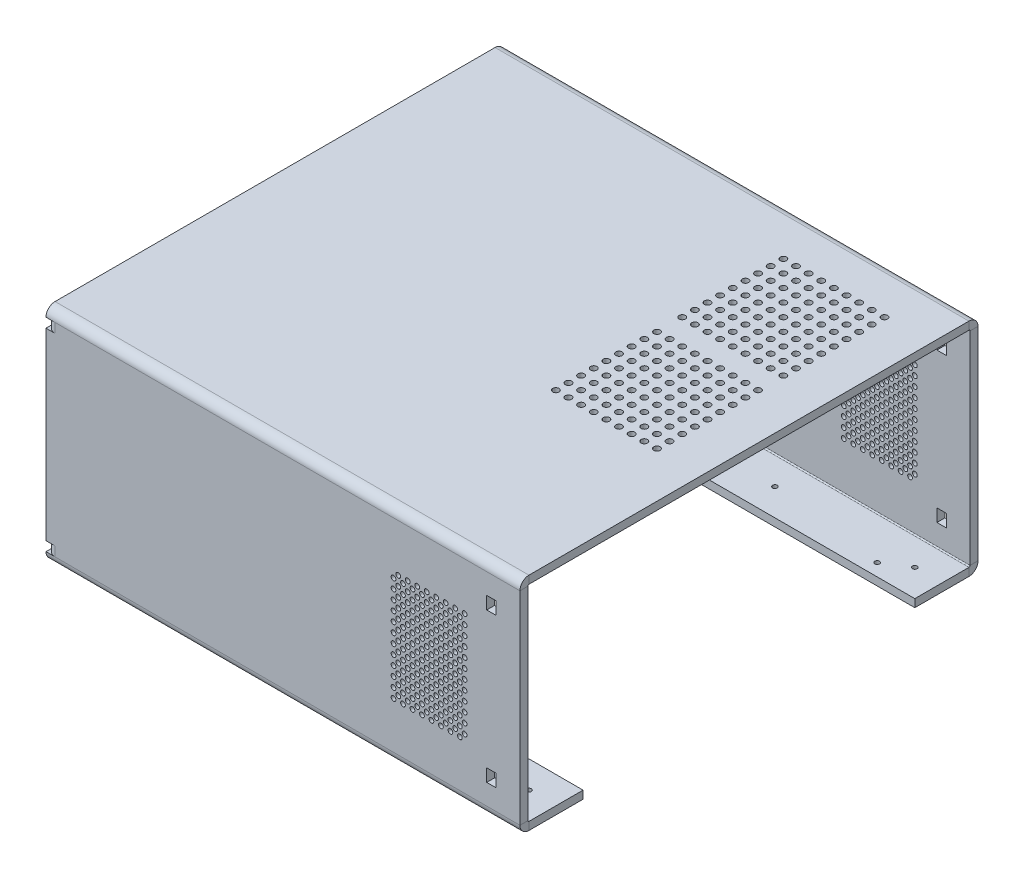
SolidWorks part; units mm, degrees
note: The reader was unsure of these and kept them because the rebuilt part matched: flange length of "Sides", "Bottom surfaces", "Edge-Flange4", "Edge-Flange5", "Edge-Flange6", "Edge-Flange7".
ref_plane "Front Plane" through (0, 0, 0) normal (0, 0, 1) x (1, 0, 0)
ref_plane "Top Plane" through (0, 0, 0) normal (0, 1, 0) x (1, 0, 0)
ref_plane "Right Plane" through (0, 0, 0) normal (1, 0, 0) x (0, 0, -1)
sketch "Sketch1" plane through (0, 0, 0) normal (0, 1, 0) x (1, 0, 0)
  line L1 (0, 0) -> (300, 0)
  line L2 (0, 0) -> (0, -280)
  line L3 (0, -280) -> (300, -280)
  line L4 (300, 0) -> (300, -280)
  dimension "D1" = 300
  dimension "D2" = 280
base flange "Top Surface" sketch "Sketch1" thickness 5 reverse thickness direction no parameters "D1"=0.7366
edge flange "Sides" sketch "Sketch10" flange profiles "Sketch10", "Sketch11" flange angle 90 flange length 140 flange position material outside bend radius 0.7366 thickness 5 relief rectangular parameters "D6"=10, "D8"=1
sketch "Sketch10" plane through (0, -5, 280) normal (0, 0, 1) x (-1, 0, 0)
  line L0 (0, 0) -> (-300, 0) construction
  line L1 (0, 0) -> (-300, 0)
  line L2 (-300, 0) -> (-300, 135)
  line L3 (-300, 135) -> (0, 135)
  line L4 (0, 135) -> (0, 0)
  dimension "D1" = 135
sketch "Sketch11" plane through (0, -5, 0) normal (0, 0, -1) x (1, 0, 0)
  line L0 (300, 0) -> (0, 0) construction
  line L1 (300, 0) -> (0, 0)
  line L2 (0, 0) -> (0, 135)
  line L3 (0, 135) -> (300, 135)
  line L4 (300, 135) -> (300, 0)
  line L7 (300, 135) -> (0, 135) construction
bend "EdgeBend1" bend radius 0.7366 bend angle 90 parameters "D5"=1
bend "EdgeBend2" bend radius 0.7366 bend angle 90 parameters "D5"=2
edge flange "Bottom surfaces" sketch "Sketch16" flange profiles "Sketch16", "Sketch17" flange angle 90 flange length 40 bend radius 0.7366 thickness 5 relief rectangular parameters "D6"=10, "D8"=1
sketch "Sketch16" plane through (0, -140, 280) normal (0, -1, 0) x (-1, 0, 0)
  line L2 (-300, 0) -> (-300, 35)
  line L3 (-300, 35) -> (0, 35)
  line L4 (0, 35) -> (0, 0)
  line L7 (0, 0) -> (-300, 0) construction
  line L8 (0, 0) -> (-300, 0)
sketch "Sketch17" plane through (0, -140, 0) normal (0, -1, 0) x (1, 0, 0)
  line L0 (300, 0) -> (0, 0) construction
  line L1 (300, 0) -> (0, 0)
  line L2 (0, 0) -> (0, 35)
  line L3 (0, 35) -> (300, 35)
  line L4 (300, 35) -> (300, 0)
bend "EdgeBend3" bend radius 0.7366 bend angle 90 parameters "D5"=3
bend "EdgeBend4" bend radius 0.7366 bend angle 90 parameters "D5"=4
sketch "Sketch27" plane through (0, -135, 0) normal (0, 1, 0) x (1, 0, 0)
  line L0 (17.1317, -17.8683) -> (17.1317, -262.1317) construction
  line L1 (17.1317, -262.1317) -> (105.7106, -262.1317) construction
  line L2 (105.7106, -262.1317) -> (194.2894, -262.1317) construction
  line L3 (194.2894, -262.1317) -> (282.8683, -262.1317) construction
  line L4 (282.8683, -262.1317) -> (282.8683, -17.8683) construction
  line L5 (282.8683, -17.8683) -> (194.2894, -17.8683) construction
  line L6 (194.2894, -17.8683) -> (105.7106, -17.8683) construction
  line L7 (105.7106, -17.8683) -> (105.7106, -262.1317) construction
  line L8 (17.1317, -17.8683) -> (105.7106, -17.8683) construction
  line L9 (194.2894, -17.8683) -> (194.2894, -262.1317) construction
  line L10 (17.1317, -17.8683) -> (0, -17.8683) construction
  line L11 (0, -35) -> (0, -0.7366) construction
  line L12 (282.8683, -17.8683) -> (300, -17.8683) construction
  line L13 (300, -0.7366) -> (300, -35) construction
  line L14 (17.1317, -17.8683) -> (17.1317, 5) construction
  line L15 (300, 5) -> (0, 5) construction
  line L16 (17.1317, -262.1317) -> (17.1317, -285) construction
  line L17 (0, -285) -> (300, -285) construction
  line L18 (17.1317, -262.1317) -> (0, -245) construction
  line L19 (17.1317, -262.1317) -> (0, -279.2634) construction
  line L20 (17.1317, -262.1317) -> (0, -262.1317) construction
  line L21 (0, -279.2634) -> (0, -245) construction
  line L22 (105.7106, -262.1317) -> (105.7106, -279.2634) construction
  line L23 (300, -279.2634) -> (0, -279.2634) construction
  circle A0 centre (17.1317, -17.8683) radius 1.5
  circle A1 centre (105.7106, -17.8683) radius 1.5
  circle A2 centre (194.2894, -17.8683) radius 1.5
  circle A3 centre (282.8683, -17.8683) radius 1.5
  circle A4 centre (17.1317, -262.1317) radius 1.5
  circle A5 centre (105.7106, -262.1317) radius 1.5
  circle A6 centre (194.2894, -262.1317) radius 1.5
  circle A7 centre (282.8683, -262.1317) radius 1.5
  dimension "D1" = 3
extrude "Screw Holes Bottom" cut sketch "Sketch27" against normal up to surface (5 mm away) normal cut yes up to face at (150, -140, 262.1317)
edge flange "Edge-Flange4" sketch "Sketch30" flange angle 90 flange length 11 flange position material inside bend radius 0.7366 thickness 5 relief none parameters "D6"=10
sketch "Sketch30" plane through (0, 0, 280) normal (-1, 0, 0) x (0, 1, 0)
  line L0 (-5.7366, 0) -> (-134.2634, 0) construction
  line L1 (-5.7366, 0) -> (-11.7366, 0)
  line L2 (-11.7366, 0) -> (-11.7366, 6)
  line L3 (-11.7366, 6) -> (-5.7366, 6)
  line L4 (-5.7366, 6) -> (-5.7366, 0)
  dimension "D1" = 6
  dimension "D2" = 6
bend "EdgeBend6" bend radius 0.7366 bend angle 90 parameters "D5"=5
edge flange "Edge-Flange5" sketch "Sketch33" flange angle 90 flange length 11 bend radius 0.7366 thickness 5 parameters "D6"=10
sketch "Sketch33" plane through (0, 0, 280) normal (-1, 0, 0) x (0, 1, 0)
  line L2 (-134.2634, 0) -> (-134.2634, 6)
  line L3 (-134.2634, 6) -> (-128.2634, 6)
  line L4 (-128.2634, 6) -> (-128.2634, 0)
  line L7 (-11.7366, 0) -> (-134.2634, 0) construction
  line L8 (-128.2634, 0) -> (-134.2634, 0)
  dimension "D1" = 6
  dimension "D2" = 6
bend "EdgeBend7" bend radius 0.7366 bend angle 90 parameters "D5"=6
edge flange "Edge-Flange6" sketch "Sketch36" flange angle 90 flange length 11 bend radius 0.7366 thickness 5 relief none parameters "D6"=10
sketch "Sketch36" plane through (0, 0, 0) normal (-1, 0, 0) x (0, -1, 0)
  line L0 (134.2634, 0) -> (5.7366, 0) construction
  line L1 (134.2634, 0) -> (128.2634, 0)
  line L2 (128.2634, 0) -> (128.2634, 6)
  line L3 (128.2634, 6) -> (134.2634, 6)
  line L4 (134.2634, 6) -> (134.2634, 0)
  dimension "D1" = 6
  dimension "D2" = 6
bend "EdgeBend8" bend radius 0.7366 bend angle 90 parameters "D5"=7
edge flange "Edge-Flange7" sketch "Sketch39" flange angle 90 flange length 11 bend radius 0.7366 thickness 5 relief none parameters "D6"=10
sketch "Sketch39" plane through (0, 0, 0) normal (-1, 0, 0) x (0, -1, 0)
  line L2 (5.7366, 0) -> (5.7366, 6)
  line L3 (5.7366, 6) -> (11.7366, 6)
  line L4 (11.7366, 6) -> (11.7366, 0)
  line L7 (128.2634, 0) -> (5.7366, 0) construction
  line L8 (11.7366, 0) -> (5.7366, 0)
  dimension "D1" = 6
  dimension "D2" = 6
bend "EdgeBend9" bend radius 0.7366 bend angle 90 parameters "D5"=8
sketch "Sketch40" plane through (0, 0, 0) normal (-1, 0, 0) x (0, 0, 1)
  line L0 (0.7366, -5.7366) -> (6, -11.7366) construction
  line L1 (6, -5.7366) -> (0.7366, -11.7366) construction
  line L4 (0.7366, -134.2634) -> (6, -128.2634) construction
  line L5 (0.7366, -128.2634) -> (6, -134.2634) construction
  line L6 (274, -128.2634) -> (279.2634, -134.2634) construction
  line L7 (279.2634, -128.2634) -> (274, -134.2634) construction
  line L8 (274, -134.2634) -> (279.2634, -134.2634) construction
  line L9 (274, -5.7366) -> (279.2634, -11.7366) construction
  line L10 (279.2634, -5.7366) -> (274, -11.7366) construction
  circle A0 centre (3.3683, -8.7366) radius 1.5
  circle A1 centre (3.3683, -131.2634) radius 1.5
  circle A2 centre (276.6317, -8.7366) radius 1.5
  circle A3 centre (276.6317, -131.2634) radius 1.5
  dimension "D1" = 3
extrude "Cut-Extrude3" cut sketch "Sketch40" against normal up to surface (5 mm away) normal cut yes up to face at (5, -8.7366, 3.3683)
sketch "Sketch42" plane through (0, 0, -5) normal (0, 0, -1) x (-1, 0, 0)
  line L0 (-265, -35.7366) -> (-265, -5.7366) construction
  line L1 (-300, -5.7366) -> (-5.7366, -5.7366) construction
  line L2 (-265, -35.7366) -> (-300, -35.7366) construction
  line L3 (-300, -5.7366) -> (-300, -134.2634) construction
  line L4 (-265, -35.7366) -> (-259, -35.7366) construction
  line L5 (-262, -38.7366) -> (-262, -35.7366) construction
  line L6 (-262, -38.7366) -> (-265, -35.7366) construction
  line L7 (-259, -35.7366) -> (-262, -38.7366) construction
  line L8 (-265, -41.7366) -> (-265, -11.7366) construction
  line L9 (-265, -53.7366) -> (-265, -23.7366) construction
  line L10 (-265, -53.7366) -> (-300, -53.7366) construction
  line L11 (-265, -53.7366) -> (-259, -53.7366) construction
  line L12 (-262, -56.7366) -> (-262, -53.7366) construction
  line L14 (-262, -56.7366) -> (-265, -53.7366) construction
  line L20 (-265, -47.7366) -> (-300, -47.7366) construction
  line L21 (-265, -41.7366) -> (-300, -41.7366) construction
  line L22 (-265, -47.7366) -> (-265, -17.7366) construction
  line L23 (-265, -41.7366) -> (-259, -41.7366) construction
  line L24 (-262, -44.7366) -> (-262, -41.7366) construction
  line L25 (-262, -44.7366) -> (-265, -41.7366) construction
  line L26 (-259, -41.7366) -> (-262, -44.7366) construction
  line L27 (-265, -47.7366) -> (-259, -47.7366) construction
  line L28 (-262, -50.7366) -> (-262, -47.7366) construction
  line L29 (-259, -47.7366) -> (-262, -50.7366) construction
  line L30 (-262, -50.7366) -> (-265, -47.7366) construction
  line L31 (-259, -53.7366) -> (-262, -56.7366) construction
  line L32 (-265, -59.7366) -> (-265, -29.7366) construction
  line L33 (-265, -59.7366) -> (-300, -59.7366) construction
  line L34 (-265, -59.7366) -> (-259, -59.7366) construction
  line L35 (-262, -62.7366) -> (-262, -59.7366) construction
  line L36 (-262, -62.7366) -> (-265, -59.7366) construction
  line L37 (-259, -59.7366) -> (-262, -62.7366) construction
  line L38 (-265, -65.7366) -> (-265, -35.7366) construction
  line L39 (-265, -65.7366) -> (-300, -65.7366) construction
  line L40 (-265, -65.7366) -> (-259, -65.7366) construction
  line L41 (-262, -68.7366) -> (-262, -65.7366) construction
  line L42 (-262, -68.7366) -> (-265, -65.7366) construction
  line L43 (-259, -65.7366) -> (-262, -68.7366) construction
  line L44 (-265, -71.7366) -> (-265, -41.7366) construction
  line L45 (-265, -71.7366) -> (-300, -71.7366) construction
  line L46 (-265, -71.7366) -> (-259, -71.7366) construction
  line L47 (-262, -74.7366) -> (-262, -71.7366) construction
  line L48 (-262, -74.7366) -> (-265, -71.7366) construction
  line L49 (-259, -71.7366) -> (-262, -74.7366) construction
  line L50 (-265, -77.7366) -> (-265, -47.7366) construction
  line L51 (-265, -77.7366) -> (-300, -77.7366) construction
  line L52 (-265, -77.7366) -> (-259, -77.7366) construction
  line L53 (-262, -80.7366) -> (-262, -77.7366) construction
  line L54 (-262, -80.7366) -> (-265, -77.7366) construction
  line L55 (-259, -77.7366) -> (-262, -80.7366) construction
  line L56 (-265, -83.7366) -> (-265, -53.7366) construction
  line L57 (-265, -83.7366) -> (-300, -83.7366) construction
  line L58 (-265, -83.7366) -> (-259, -83.7366) construction
  line L59 (-262, -86.7366) -> (-262, -83.7366) construction
  line L60 (-262, -86.7366) -> (-265, -83.7366) construction
  line L61 (-259, -83.7366) -> (-262, -86.7366) construction
  line L62 (-265, -89.7366) -> (-265, -59.7366) construction
  line L63 (-265, -89.7366) -> (-300, -89.7366) construction
  line L64 (-265, -89.7366) -> (-259, -89.7366) construction
  line L65 (-262, -92.7366) -> (-262, -89.7366) construction
  line L66 (-262, -92.7366) -> (-265, -89.7366) construction
  line L67 (-259, -89.7366) -> (-262, -92.7366) construction
  line L68 (-265, -95.7366) -> (-265, -65.7366) construction
  line L69 (-265, -95.7366) -> (-300, -95.7366) construction
  line L70 (-265, -95.7366) -> (-259, -95.7366) construction
  line L71 (-262, -98.7366) -> (-262, -95.7366) construction
  line L72 (-262, -98.7366) -> (-265, -95.7366) construction
  line L73 (-259, -95.7366) -> (-262, -98.7366) construction
  line L74 (-265, -101.7366) -> (-265, -71.7366) construction
  line L75 (-265, -101.7366) -> (-300, -101.7366) construction
  line L76 (-265, -101.7366) -> (-259, -101.7366) construction
  line L77 (-262, -104.7366) -> (-262, -101.7366) construction
  line L78 (-262, -104.7366) -> (-265, -101.7366) construction
  line L79 (-259, -101.7366) -> (-262, -104.7366) construction
  circle A0 centre (-265, -35.7366) radius 1.5
  circle A1 centre (-259, -35.7366) radius 1.5
  circle A2 centre (-253, -35.7366) radius 1.5
  circle A3 centre (-247, -35.7366) radius 1.5
  circle A4 centre (-241, -35.7366) radius 1.5
  circle A5 centre (-235, -35.7366) radius 1.5
  circle A6 centre (-229, -35.7366) radius 1.5
  circle A7 centre (-223, -35.7366) radius 1.5
  circle A16 centre (-262, -38.7366) radius 1.5
  circle A17 centre (-256, -38.7366) radius 1.5
  circle A18 centre (-250, -38.7366) radius 1.5
  circle A19 centre (-244, -38.7366) radius 1.5
  circle A20 centre (-238, -38.7366) radius 1.5
  circle A21 centre (-232, -38.7366) radius 1.5
  circle A22 centre (-226, -38.7366) radius 1.5
  circle A23 centre (-220, -38.7366) radius 1.5
  circle A24 centre (-265, -41.7366) radius 1.5
  circle A25 centre (-259, -41.7366) radius 1.5
  circle A26 centre (-253, -41.7366) radius 1.5
  circle A27 centre (-247, -41.7366) radius 1.5
  circle A28 centre (-241, -41.7366) radius 1.5
  circle A29 centre (-235, -41.7366) radius 1.5
  circle A30 centre (-229, -41.7366) radius 1.5
  circle A31 centre (-223, -41.7366) radius 1.5
  circle A32 centre (-262, -44.7366) radius 1.5
  circle A33 centre (-256, -44.7366) radius 1.5
  circle A34 centre (-250, -44.7366) radius 1.5
  circle A35 centre (-244, -44.7366) radius 1.5
  circle A36 centre (-238, -44.7366) radius 1.5
  circle A37 centre (-232, -44.7366) radius 1.5
  circle A38 centre (-226, -44.7366) radius 1.5
  circle A39 centre (-220, -44.7366) radius 1.5
  circle A40 centre (-265, -47.7366) radius 1.5
  circle A41 centre (-259, -47.7366) radius 1.5
  circle A42 centre (-253, -47.7366) radius 1.5
  circle A43 centre (-247, -47.7366) radius 1.5
  circle A44 centre (-241, -47.7366) radius 1.5
  circle A45 centre (-235, -47.7366) radius 1.5
  circle A46 centre (-229, -47.7366) radius 1.5
  circle A47 centre (-223, -47.7366) radius 1.5
  circle A48 centre (-262, -50.7366) radius 1.5
  circle A49 centre (-256, -50.7366) radius 1.5
  circle A50 centre (-250, -50.7366) radius 1.5
  circle A51 centre (-244, -50.7366) radius 1.5
  circle A52 centre (-238, -50.7366) radius 1.5
  circle A53 centre (-232, -50.7366) radius 1.5
  circle A54 centre (-226, -50.7366) radius 1.5
  circle A55 centre (-220, -50.7366) radius 1.5
  circle A56 centre (-265, -53.7366) radius 1.5
  circle A57 centre (-259, -53.7366) radius 1.5
  circle A58 centre (-253, -53.7366) radius 1.5
  circle A59 centre (-247, -53.7366) radius 1.5
  circle A60 centre (-241, -53.7366) radius 1.5
  circle A61 centre (-235, -53.7366) radius 1.5
  circle A62 centre (-229, -53.7366) radius 1.5
  circle A63 centre (-223, -53.7366) radius 1.5
  circle A64 centre (-262, -56.7366) radius 1.5
  circle A65 centre (-256, -56.7366) radius 1.5
  circle A66 centre (-250, -56.7366) radius 1.5
  circle A67 centre (-244, -56.7366) radius 1.5
  circle A68 centre (-238, -56.7366) radius 1.5
  circle A69 centre (-232, -56.7366) radius 1.5
  circle A70 centre (-226, -56.7366) radius 1.5
  circle A71 centre (-220, -56.7366) radius 1.5
  circle A72 centre (-265, -59.7366) radius 1.5
  circle A73 centre (-259, -59.7366) radius 1.5
  circle A74 centre (-253, -59.7366) radius 1.5
  circle A75 centre (-247, -59.7366) radius 1.5
  circle A76 centre (-241, -59.7366) radius 1.5
  circle A77 centre (-235, -59.7366) radius 1.5
  circle A78 centre (-229, -59.7366) radius 1.5
  circle A79 centre (-223, -59.7366) radius 1.5
  circle A80 centre (-262, -62.7366) radius 1.5
  circle A81 centre (-256, -62.7366) radius 1.5
  circle A82 centre (-250, -62.7366) radius 1.5
  circle A83 centre (-244, -62.7366) radius 1.5
  circle A84 centre (-238, -62.7366) radius 1.5
  circle A85 centre (-232, -62.7366) radius 1.5
  circle A86 centre (-226, -62.7366) radius 1.5
  circle A87 centre (-220, -62.7366) radius 1.5
  circle A88 centre (-265, -65.7366) radius 1.5
  circle A89 centre (-259, -65.7366) radius 1.5
  circle A90 centre (-253, -65.7366) radius 1.5
  circle A91 centre (-247, -65.7366) radius 1.5
  circle A92 centre (-241, -65.7366) radius 1.5
  circle A93 centre (-235, -65.7366) radius 1.5
  circle A94 centre (-229, -65.7366) radius 1.5
  circle A95 centre (-223, -65.7366) radius 1.5
  circle A96 centre (-262, -68.7366) radius 1.5
  circle A97 centre (-256, -68.7366) radius 1.5
  circle A98 centre (-250, -68.7366) radius 1.5
  circle A99 centre (-244, -68.7366) radius 1.5
  circle A100 centre (-238, -68.7366) radius 1.5
  circle A101 centre (-232, -68.7366) radius 1.5
  circle A102 centre (-226, -68.7366) radius 1.5
  circle A103 centre (-220, -68.7366) radius 1.5
  circle A104 centre (-265, -71.7366) radius 1.5
  circle A105 centre (-259, -71.7366) radius 1.5
  circle A106 centre (-253, -71.7366) radius 1.5
  circle A107 centre (-247, -71.7366) radius 1.5
  circle A108 centre (-241, -71.7366) radius 1.5
  circle A109 centre (-235, -71.7366) radius 1.5
  circle A110 centre (-229, -71.7366) radius 1.5
  circle A111 centre (-223, -71.7366) radius 1.5
  circle A112 centre (-262, -74.7366) radius 1.5
  circle A113 centre (-256, -74.7366) radius 1.5
  circle A114 centre (-250, -74.7366) radius 1.5
  circle A115 centre (-244, -74.7366) radius 1.5
  circle A116 centre (-238, -74.7366) radius 1.5
  circle A117 centre (-232, -74.7366) radius 1.5
  circle A118 centre (-226, -74.7366) radius 1.5
  circle A119 centre (-220, -74.7366) radius 1.5
  circle A120 centre (-265, -77.7366) radius 1.5
  circle A121 centre (-259, -77.7366) radius 1.5
  circle A122 centre (-253, -77.7366) radius 1.5
  circle A123 centre (-247, -77.7366) radius 1.5
  circle A124 centre (-241, -77.7366) radius 1.5
  circle A125 centre (-235, -77.7366) radius 1.5
  circle A126 centre (-229, -77.7366) radius 1.5
  circle A127 centre (-223, -77.7366) radius 1.5
  circle A128 centre (-262, -80.7366) radius 1.5
  circle A129 centre (-256, -80.7366) radius 1.5
  circle A130 centre (-250, -80.7366) radius 1.5
  circle A131 centre (-244, -80.7366) radius 1.5
  circle A132 centre (-238, -80.7366) radius 1.5
  circle A133 centre (-232, -80.7366) radius 1.5
  circle A134 centre (-226, -80.7366) radius 1.5
  circle A135 centre (-220, -80.7366) radius 1.5
  circle A136 centre (-265, -83.7366) radius 1.5
  circle A137 centre (-259, -83.7366) radius 1.5
  circle A138 centre (-253, -83.7366) radius 1.5
  circle A139 centre (-247, -83.7366) radius 1.5
  circle A140 centre (-241, -83.7366) radius 1.5
  circle A141 centre (-235, -83.7366) radius 1.5
  circle A142 centre (-229, -83.7366) radius 1.5
  circle A143 centre (-223, -83.7366) radius 1.5
  circle A144 centre (-262, -86.7366) radius 1.5
  circle A145 centre (-256, -86.7366) radius 1.5
  circle A146 centre (-250, -86.7366) radius 1.5
  circle A147 centre (-244, -86.7366) radius 1.5
  circle A148 centre (-238, -86.7366) radius 1.5
  circle A149 centre (-232, -86.7366) radius 1.5
  circle A150 centre (-226, -86.7366) radius 1.5
  circle A151 centre (-220, -86.7366) radius 1.5
  circle A152 centre (-265, -89.7366) radius 1.5
  circle A153 centre (-259, -89.7366) radius 1.5
  circle A154 centre (-253, -89.7366) radius 1.5
  circle A155 centre (-247, -89.7366) radius 1.5
  circle A156 centre (-241, -89.7366) radius 1.5
  circle A157 centre (-235, -89.7366) radius 1.5
  circle A158 centre (-229, -89.7366) radius 1.5
  circle A159 centre (-223, -89.7366) radius 1.5
  circle A160 centre (-262, -92.7366) radius 1.5
  circle A161 centre (-256, -92.7366) radius 1.5
  circle A162 centre (-250, -92.7366) radius 1.5
  circle A163 centre (-244, -92.7366) radius 1.5
  circle A164 centre (-238, -92.7366) radius 1.5
  circle A165 centre (-232, -92.7366) radius 1.5
  circle A166 centre (-226, -92.7366) radius 1.5
  circle A167 centre (-220, -92.7366) radius 1.5
  circle A168 centre (-265, -95.7366) radius 1.5
  circle A169 centre (-259, -95.7366) radius 1.5
  circle A170 centre (-253, -95.7366) radius 1.5
  circle A171 centre (-247, -95.7366) radius 1.5
  circle A172 centre (-241, -95.7366) radius 1.5
  circle A173 centre (-235, -95.7366) radius 1.5
  circle A174 centre (-229, -95.7366) radius 1.5
  circle A175 centre (-223, -95.7366) radius 1.5
  circle A176 centre (-262, -98.7366) radius 1.5
  circle A177 centre (-256, -98.7366) radius 1.5
  circle A178 centre (-250, -98.7366) radius 1.5
  circle A179 centre (-244, -98.7366) radius 1.5
  circle A180 centre (-238, -98.7366) radius 1.5
  circle A181 centre (-232, -98.7366) radius 1.5
  circle A182 centre (-226, -98.7366) radius 1.5
  circle A183 centre (-220, -98.7366) radius 1.5
  circle A184 centre (-265, -101.7366) radius 1.5
  circle A185 centre (-259, -101.7366) radius 1.5
  circle A186 centre (-253, -101.7366) radius 1.5
  circle A187 centre (-247, -101.7366) radius 1.5
  circle A188 centre (-241, -101.7366) radius 1.5
  circle A189 centre (-235, -101.7366) radius 1.5
  circle A190 centre (-229, -101.7366) radius 1.5
  circle A191 centre (-223, -101.7366) radius 1.5
  circle A192 centre (-262, -104.7366) radius 1.5
  circle A193 centre (-256, -104.7366) radius 1.5
  circle A194 centre (-250, -104.7366) radius 1.5
  circle A195 centre (-244, -104.7366) radius 1.5
  circle A196 centre (-238, -104.7366) radius 1.5
  circle A197 centre (-232, -104.7366) radius 1.5
  circle A198 centre (-226, -104.7366) radius 1.5
  circle A199 centre (-220, -104.7366) radius 1.5
  dimension "D1" = 3
  dimension "D5" = 3
  dimension "D6" = 3
  dimension "D2" = 35
  dimension "D3" = 30
  dimension "D7" = 8
  dimension "D4" = 8
  dimension "D8" = 12
extrude "Side Air Vents" cut sketch "Sketch42" against normal through all normal cut yes
sketch "Sketch46" plane through (0, 0, 0) normal (0, 1, 0) x (1, 0, 0)
  line L0 (200.7643, -140) -> (200.7643, -0.7366) construction
  line L1 (300, -0.7366) -> (0, -0.7366) construction
  line L2 (200.7643, -140) -> (200.7643, -279.2634) construction
  line L3 (0, -279.2634) -> (300, -279.2634) construction
  circle A4 centre (207.1214, -25.3668) radius 2
  circle A8 centre (207.1214, -33.3668) radius 2
  circle A12 centre (207.1214, -41.3668) radius 2
  circle A16 centre (207.1214, -49.3668) radius 2
  circle A20 centre (207.1214, -57.3668) radius 2
  circle A21 centre (207.1214, -65.3668) radius 2
  circle A22 centre (207.1214, -73.3668) radius 2
  circle A23 centre (207.1214, -81.3668) radius 2
  circle A24 centre (207.1214, -89.3668) radius 2
  circle A25 centre (215.1214, -25.3668) radius 2
  circle A26 centre (215.1214, -33.3668) radius 2
  circle A27 centre (215.1214, -41.3668) radius 2
  circle A28 centre (215.1214, -49.3668) radius 2
  circle A29 centre (215.1214, -57.3668) radius 2
  circle A30 centre (215.1214, -65.3668) radius 2
  circle A31 centre (215.1214, -73.3668) radius 2
  circle A32 centre (215.1214, -81.3668) radius 2
  circle A33 centre (215.1214, -89.3668) radius 2
  circle A34 centre (223.1214, -25.3668) radius 2
  circle A35 centre (223.1214, -33.3668) radius 2
  circle A36 centre (223.1214, -41.3668) radius 2
  circle A37 centre (223.1214, -49.3668) radius 2
  circle A38 centre (223.1214, -57.3668) radius 2
  circle A39 centre (223.1214, -65.3668) radius 2
  circle A40 centre (223.1214, -73.3668) radius 2
  circle A41 centre (223.1214, -81.3668) radius 2
  circle A42 centre (223.1214, -89.3668) radius 2
  circle A43 centre (231.1214, -25.3668) radius 2
  circle A44 centre (231.1214, -33.3668) radius 2
  circle A45 centre (231.1214, -41.3668) radius 2
  circle A46 centre (231.1214, -49.3668) radius 2
  circle A47 centre (231.1214, -57.3668) radius 2
  circle A48 centre (231.1214, -65.3668) radius 2
  circle A49 centre (231.1214, -73.3668) radius 2
  circle A50 centre (231.1214, -81.3668) radius 2
  circle A51 centre (231.1214, -89.3668) radius 2
  circle A52 centre (239.1214, -25.3668) radius 2
  circle A53 centre (239.1214, -33.3668) radius 2
  circle A54 centre (239.1214, -41.3668) radius 2
  circle A55 centre (239.1214, -49.3668) radius 2
  circle A56 centre (239.1214, -57.3668) radius 2
  circle A57 centre (239.1214, -65.3668) radius 2
  circle A58 centre (239.1214, -73.3668) radius 2
  circle A59 centre (239.1214, -81.3668) radius 2
  circle A60 centre (239.1214, -89.3668) radius 2
  circle A61 centre (247.1214, -25.3668) radius 2
  circle A62 centre (247.1214, -33.3668) radius 2
  circle A63 centre (247.1214, -41.3668) radius 2
  circle A64 centre (247.1214, -49.3668) radius 2
  circle A65 centre (247.1214, -57.3668) radius 2
  circle A66 centre (247.1214, -65.3668) radius 2
  circle A67 centre (247.1214, -73.3668) radius 2
  circle A68 centre (247.1214, -81.3668) radius 2
  circle A69 centre (247.1214, -89.3668) radius 2
  circle A70 centre (255.1214, -25.3668) radius 2
  circle A71 centre (255.1214, -33.3668) radius 2
  circle A72 centre (255.1214, -41.3668) radius 2
  circle A73 centre (255.1214, -49.3668) radius 2
  circle A74 centre (255.1214, -57.3668) radius 2
  circle A75 centre (255.1214, -65.3668) radius 2
  circle A76 centre (255.1214, -73.3668) radius 2
  circle A77 centre (255.1214, -81.3668) radius 2
  circle A78 centre (255.1214, -89.3668) radius 2
  circle A79 centre (263.1214, -25.3668) radius 2
  circle A80 centre (263.1214, -33.3668) radius 2
  circle A81 centre (263.1214, -41.3668) radius 2
  circle A82 centre (263.1214, -49.3668) radius 2
  circle A83 centre (263.1214, -57.3668) radius 2
  circle A84 centre (263.1214, -65.3668) radius 2
  circle A85 centre (263.1214, -73.3668) radius 2
  circle A86 centre (263.1214, -81.3668) radius 2
  circle A87 centre (263.1214, -89.3668) radius 2
  circle A88 centre (271.1214, -25.3668) radius 2
  circle A89 centre (271.1214, -33.3668) radius 2
  circle A90 centre (271.1214, -41.3668) radius 2
  circle A91 centre (271.1214, -49.3668) radius 2
  circle A92 centre (271.1214, -57.3668) radius 2
  circle A93 centre (271.1214, -65.3668) radius 2
  circle A94 centre (271.1214, -73.3668) radius 2
  circle A95 centre (271.1214, -81.3668) radius 2
  circle A96 centre (271.1214, -89.3668) radius 2
  circle A97 centre (207.1214, -105.3668) radius 2
  circle A98 centre (207.1214, -113.3668) radius 2
  circle A99 centre (207.1214, -121.3668) radius 2
  circle A100 centre (207.1214, -129.3668) radius 2
  circle A101 centre (207.1214, -137.3668) radius 2
  circle A102 centre (207.1214, -145.3668) radius 2
  circle A103 centre (207.1214, -153.3668) radius 2
  circle A104 centre (207.1214, -161.3668) radius 2
  circle A105 centre (207.1214, -169.3668) radius 2
  circle A106 centre (215.1214, -105.3668) radius 2
  circle A107 centre (215.1214, -113.3668) radius 2
  circle A108 centre (215.1214, -121.3668) radius 2
  circle A109 centre (215.1214, -129.3668) radius 2
  circle A110 centre (215.1214, -137.3668) radius 2
  circle A111 centre (215.1214, -145.3668) radius 2
  circle A112 centre (215.1214, -153.3668) radius 2
  circle A113 centre (215.1214, -161.3668) radius 2
  circle A114 centre (215.1214, -169.3668) radius 2
  circle A115 centre (223.1214, -105.3668) radius 2
  circle A116 centre (223.1214, -113.3668) radius 2
  circle A117 centre (223.1214, -121.3668) radius 2
  circle A118 centre (223.1214, -129.3668) radius 2
  circle A119 centre (223.1214, -137.3668) radius 2
  circle A120 centre (223.1214, -145.3668) radius 2
  circle A121 centre (223.1214, -153.3668) radius 2
  circle A122 centre (223.1214, -161.3668) radius 2
  circle A123 centre (223.1214, -169.3668) radius 2
  circle A124 centre (231.1214, -105.3668) radius 2
  circle A125 centre (231.1214, -113.3668) radius 2
  circle A126 centre (231.1214, -121.3668) radius 2
  circle A127 centre (231.1214, -129.3668) radius 2
  circle A128 centre (231.1214, -137.3668) radius 2
  circle A129 centre (231.1214, -145.3668) radius 2
  circle A130 centre (231.1214, -153.3668) radius 2
  circle A131 centre (231.1214, -161.3668) radius 2
  circle A132 centre (231.1214, -169.3668) radius 2
  circle A133 centre (239.1214, -105.3668) radius 2
  circle A134 centre (239.1214, -113.3668) radius 2
  circle A135 centre (239.1214, -121.3668) radius 2
  circle A136 centre (239.1214, -129.3668) radius 2
  circle A137 centre (239.1214, -137.3668) radius 2
  circle A138 centre (239.1214, -145.3668) radius 2
  circle A139 centre (239.1214, -153.3668) radius 2
  circle A140 centre (239.1214, -161.3668) radius 2
  circle A141 centre (239.1214, -169.3668) radius 2
  circle A142 centre (247.1214, -105.3668) radius 2
  circle A143 centre (247.1214, -113.3668) radius 2
  circle A144 centre (247.1214, -121.3668) radius 2
  circle A145 centre (247.1214, -129.3668) radius 2
  circle A146 centre (247.1214, -137.3668) radius 2
  circle A147 centre (247.1214, -145.3668) radius 2
  circle A148 centre (247.1214, -153.3668) radius 2
  circle A149 centre (247.1214, -161.3668) radius 2
  circle A150 centre (247.1214, -169.3668) radius 2
  circle A151 centre (255.1214, -105.3668) radius 2
  circle A152 centre (255.1214, -113.3668) radius 2
  circle A153 centre (255.1214, -121.3668) radius 2
  circle A154 centre (255.1214, -129.3668) radius 2
  circle A155 centre (255.1214, -137.3668) radius 2
  circle A156 centre (255.1214, -145.3668) radius 2
  circle A157 centre (255.1214, -153.3668) radius 2
  circle A158 centre (255.1214, -161.3668) radius 2
  circle A159 centre (255.1214, -169.3668) radius 2
  circle A160 centre (263.1214, -105.3668) radius 2
  circle A161 centre (263.1214, -113.3668) radius 2
  circle A162 centre (263.1214, -121.3668) radius 2
  circle A163 centre (263.1214, -129.3668) radius 2
  circle A164 centre (263.1214, -137.3668) radius 2
  circle A165 centre (263.1214, -145.3668) radius 2
  circle A166 centre (263.1214, -153.3668) radius 2
  circle A167 centre (263.1214, -161.3668) radius 2
  circle A168 centre (263.1214, -169.3668) radius 2
  circle A169 centre (271.1214, -105.3668) radius 2
  circle A170 centre (271.1214, -113.3668) radius 2
  circle A171 centre (271.1214, -121.3668) radius 2
  circle A172 centre (271.1214, -129.3668) radius 2
  circle A173 centre (271.1214, -137.3668) radius 2
  circle A174 centre (271.1214, -145.3668) radius 2
  circle A175 centre (271.1214, -153.3668) radius 2
  circle A176 centre (271.1214, -161.3668) radius 2
  circle A177 centre (271.1214, -169.3668) radius 2
  dimension "D1" = 9
  dimension "D2" = 2
extrude "Top Air Vents" cut sketch "Sketch46" against normal up to surface (5 mm away) normal cut yes up to face at (150, -5, 140)
sketch "Sketch43" plane through (0, 0, 285) normal (0, 0, 1) x (1, 0, 0)
  line L0 (279, -18.7366) -> (279, -5.7366) construction
  line L1 (279, -18.7366) -> (285, -18.7366)
  line L2 (279, -18.7366) -> (279, -26.7366)
  line L3 (279, -26.7366) -> (285, -26.7366)
  line L4 (285, -18.7366) -> (285, -26.7366)
  line L5 (279, -113.2634) -> (285, -113.2634)
  line L6 (279, -113.2634) -> (279, -121.2634)
  line L7 (279, -121.2634) -> (285, -121.2634)
  line L8 (285, -113.2634) -> (285, -121.2634)
  line L9 (5.7366, -5.7366) -> (300, -5.7366) construction
  line L10 (279, -121.2634) -> (279, -134.2634) construction
  line L11 (5.7366, -134.2634) -> (300, -134.2634) construction
  line L12 (300, -134.2634) -> (300, -5.7366) construction
  dimension "D1" = 6
  dimension "D2" = 8
  dimension "D3" = 13
  dimension "D4" = 15
extrude "Snap Hook Groves" cut sketch "Sketch43" against normal up to surface (290 mm away) up to face at (265, -82.2366, -5)
sketch "Sketch47" plane through (0, -135, 0) normal (0, 1, 0) x (1, 0, 0)
  circle A0 centre (268.313, -27.1322) radius 1.5
  circle A1 centre (31.763, -27.1322) radius 1.5
extrude "Cut-Extrude4" cut sketch "Sketch47" against normal blind 10
sketch "Bend-Lines1" [suppressed] plane through (0, 0, 0) normal (0, 1, 0) x (1, 0, 0)
sketch "Bounding-Box1" [suppressed] plane through (0, 0, 0) normal (0, 1, 0) x (1, 0, 0)
sheet metal parameters "Sheet-Metal1" thickness 5 parameters "D1"=0.7366
flat pattern "Flat-Pattern1" [suppressed]
sketch "Bend-Lines2" plane through (0, 0, 0) normal (0, 1, 0) x (1, 0, 0)
sketch3d "Bounding-Box2" [suppressed]
  line L0 (-300, -250, 0) -> (0, -250, 0) construction
  line L1 (-300, 0, 0) -> (0, 0, 0) construction
  line L2 (-300, -250, 0) -> (-300, 0, 0) construction
  line L3 (0, -250, 0) -> (0, 0, 0) construction
sheet metal parameters "Sheet-Metal2" thickness 5 parameters "D1"=0.7366
flat pattern "Flat-Pattern1" [suppressed]
sketch "Bend-Lines2" plane through (0, 0, 0) normal (0, 1, 0) x (1, 0, 0)
  line L0 (300, 1.8054) -> (0, 1.8054) construction
  line L1 (0, -251.8054) -> (300, -251.8054) construction
  line L2 (300, 1.8054) -> (0, 1.8054) construction
  line L3 (0, -251.8054) -> (300, -251.8054) construction
sketch3d "Bounding-Box2" [suppressed]
  line L0 (0, 98.6108, 0) -> (0, -348.6108, 0) construction
  line L1 (300, 98.6108, 0) -> (300, -348.6108, 0) construction
  line L2 (0, 98.6108, 0) -> (300, 98.6108, 0) construction
  line L3 (0, -348.6108, 0) -> (300, -348.6108, 0) construction
bend of the flat pattern "Flatten-<EdgeBend1>1"
bend of the flat pattern "Flatten-<EdgeBend2>1"
sheet metal parameters "Sheet-Metal3" thickness 5 parameters "D1"=0.7366
flat pattern "Flat-Pattern1" [suppressed]
sketch "Bend-Lines2" plane through (0, 0, 0) normal (0, 1, 0) x (1, 0, 0)
  line L0 (300, 1.8054) -> (0, 1.8054) construction
  line L1 (0, -251.8054) -> (300, -251.8054) construction
  line L2 (300, 1.8054) -> (0, 1.8054) construction
  line L3 (0, -251.8054) -> (300, -251.8054) construction
  line L4 (300, 100.4163) -> (0, 100.4163) construction
  line L5 (0, -350.4163) -> (300, -350.4163) construction
  line L6 (300, 100.4163) -> (0, 100.4163) construction
  line L7 (0, -350.4163) -> (300, -350.4163) construction
sketch3d "Bounding-Box2" [suppressed]
  line L0 (0, 137.2217, 0) -> (0, -387.2217, 0) construction
  line L1 (300, 137.2217, 0) -> (300, -387.2217, 0) construction
  line L2 (0, 137.2217, 0) -> (300, 137.2217, 0) construction
  line L3 (0, -387.2217, 0) -> (300, -387.2217, 0) construction
bend of the flat pattern "Flatten-<EdgeBend3>1"
bend of the flat pattern "Flatten-<EdgeBend4>1"
bend of the flat pattern "Flatten-<EdgeBend1>1"
bend of the flat pattern "Flatten-<EdgeBend2>1"
sheet metal parameters "Sheet-Metal7" thickness 5 parameters "D1"=0.7366
flat pattern "Flat-Pattern1" [suppressed]
sketch "Bend-Lines2" plane through (0, 0, 0) normal (0, 1, 0) x (1, 0, 0)
  line L0 (300, 1.8054) -> (0, 1.8054) construction
  line L1 (0, -251.8054) -> (300, -251.8054) construction
  line L2 (300, 1.8054) -> (0, 1.8054) construction
  line L3 (0, -251.8054) -> (300, -251.8054) construction
  line L4 (300, 100.4163) -> (0, 100.4163) construction
  line L5 (0, -350.4163) -> (300, -350.4163) construction
  line L6 (300, 100.4163) -> (0, 100.4163) construction
  line L7 (0, -350.4163) -> (300, -350.4163) construction
sketch3d "Bounding-Box2" [suppressed]
  line L0 (0, 137.2217, 0) -> (0, -387.2217, 0) construction
  line L1 (300, 137.2217, 0) -> (300, -387.2217, 0) construction
  line L2 (0, 137.2217, 0) -> (300, 137.2217, 0) construction
  line L3 (0, -387.2217, 0) -> (300, -387.2217, 0) construction
bend of the flat pattern "Flatten-<EdgeBend3>1"
bend of the flat pattern "Flatten-<EdgeBend4>1"
bend of the flat pattern "Flatten-<EdgeBend1>1"
bend of the flat pattern "Flatten-<EdgeBend2>1"
sheet metal parameters "Sheet-Metal8" thickness 5 parameters "D1"=0.7366
flat pattern "Flat-Pattern1" [suppressed]
sketch "Bend-Lines2" plane through (0, 0, 0) normal (0, 1, 0) x (1, 0, 0)
  line L0 (300, 1.8054) -> (0, 1.8054) construction
  line L1 (0, -251.8054) -> (300, -251.8054) construction
  line L2 (300, 1.8054) -> (0, 1.8054) construction
  line L3 (0, -251.8054) -> (300, -251.8054) construction
  line L4 (300, 100.4163) -> (0, 100.4163) construction
  line L5 (0, -350.4163) -> (300, -350.4163) construction
  line L6 (300, 100.4163) -> (0, 100.4163) construction
  line L7 (0, -350.4163) -> (300, -350.4163) construction
  line L8 (3.1946, -260.3474) -> (3.1946, -254.3474) construction
  line L9 (3.1946, -260.3474) -> (3.1946, -254.3474) construction
sketch3d "Bounding-Box2" [suppressed]
  line L0 (300.0004, 137.2214, 0) -> (300, -387.2217, 0) construction
  line L1 (-4.6105, 137.2217, 0) -> (-4.6109, -387.2214, 0) construction
  line L2 (300.0004, 137.2214, 0) -> (-4.6105, 137.2217, 0) construction
  line L3 (300, -387.2217, 0) -> (-4.6109, -387.2214, 0) construction
bend of the flat pattern "Flatten-<EdgeBend6>1"
bend of the flat pattern "Flatten-<EdgeBend3>1"
bend of the flat pattern "Flatten-<EdgeBend4>1"
bend of the flat pattern "Flatten-<EdgeBend1>1"
bend of the flat pattern "Flatten-<EdgeBend2>1"
sheet metal parameters "Sheet-Metal9" thickness 5 parameters "D1"=0.7366
flat pattern "Flat-Pattern1" [suppressed]
sketch "Bend-Lines2" plane through (0, 0, 0) normal (0, 1, 0) x (1, 0, 0)
  line L0 (300, 1.8054) -> (0, 1.8054) construction
  line L1 (0, -251.8054) -> (300, -251.8054) construction
  line L2 (300, 1.8054) -> (0, 1.8054) construction
  line L3 (0, -251.8054) -> (300, -251.8054) construction
  line L4 (300, 100.4163) -> (0, 100.4163) construction
  line L5 (0, -350.4163) -> (300, -350.4163) construction
  line L6 (300, 100.4163) -> (0, 100.4163) construction
  line L7 (0, -350.4163) -> (300, -350.4163) construction
  line L8 (3.1946, -260.3474) -> (3.1946, -254.3474) construction
  line L9 (3.1946, -260.3474) -> (3.1946, -254.3474) construction
  line L10 (3.1946, -347.8742) -> (3.1946, -341.8742) construction
  line L11 (3.1946, -347.8742) -> (3.1946, -341.8742) construction
sketch3d "Bounding-Box2" [suppressed]
  line L0 (300.0004, 137.2214, 0) -> (300, -387.2217, 0) construction
  line L1 (-4.6104, 137.2217, 0) -> (-4.6109, -387.2214, 0) construction
  line L2 (300.0004, 137.2214, 0) -> (-4.6104, 137.2217, 0) construction
  line L3 (300, -387.2217, 0) -> (-4.6109, -387.2214, 0) construction
bend of the flat pattern "Flatten-<EdgeBend6>1"
bend of the flat pattern "Flatten-<EdgeBend7>1"
bend of the flat pattern "Flatten-<EdgeBend3>1"
bend of the flat pattern "Flatten-<EdgeBend4>1"
bend of the flat pattern "Flatten-<EdgeBend1>1"
bend of the flat pattern "Flatten-<EdgeBend2>1"
sheet metal parameters "Sheet-Metal10" thickness 5 parameters "D1"=0.7366
flat pattern "Flat-Pattern1" [suppressed]
sketch "Bend-Lines2" plane through (0, 0, 0) normal (0, 1, 0) x (1, 0, 0)
  line L0 (300, 1.8054) -> (0, 1.8054) construction
  line L1 (0, -251.8054) -> (300, -251.8054) construction
  line L2 (300, 1.8054) -> (0, 1.8054) construction
  line L3 (0, -251.8054) -> (300, -251.8054) construction
  line L4 (300, 100.4163) -> (0, 100.4163) construction
  line L5 (0, -350.4163) -> (300, -350.4163) construction
  line L6 (300, 100.4163) -> (0, 100.4163) construction
  line L7 (0, -350.4163) -> (300, -350.4163) construction
  line L8 (3.1946, -260.3474) -> (3.1946, -254.3474) construction
  line L9 (3.1946, -260.3474) -> (3.1946, -254.3474) construction
  line L10 (3.1946, -347.8742) -> (3.1946, -341.8742) construction
  line L11 (3.1946, -347.8742) -> (3.1946, -341.8742) construction
  line L12 (3.1946, 91.8742) -> (3.1946, 97.8742) construction
  line L13 (3.1946, 91.8742) -> (3.1946, 97.8742) construction
sketch3d "Bounding-Box2" [suppressed]
  line L0 (-4.6108, 137.2217, 0) -> (-4.6108, -387.2217, 0) construction
  line L1 (300, 137.2217, 0) -> (300, -387.2217, 0) construction
  line L2 (-4.6108, 137.2217, 0) -> (300, 137.2217, 0) construction
  line L3 (-4.6108, -387.2217, 0) -> (300, -387.2217, 0) construction
bend of the flat pattern "Flatten-<EdgeBend6>1"
bend of the flat pattern "Flatten-<EdgeBend7>1"
bend of the flat pattern "Flatten-<EdgeBend8>1"
bend of the flat pattern "Flatten-<EdgeBend3>1"
bend of the flat pattern "Flatten-<EdgeBend4>1"
bend of the flat pattern "Flatten-<EdgeBend1>1"
bend of the flat pattern "Flatten-<EdgeBend2>1"
sheet metal parameters "Sheet-Metal11" thickness 5 parameters "D1"=0.7366
flat pattern "Flat-Pattern1" [suppressed]
sketch "Bend-Lines2" plane through (0, 0, 0) normal (0, 1, 0) x (1, 0, 0)
  line L0 (300, 1.8054) -> (0, 1.8054) construction
  line L1 (0, -251.8054) -> (300, -251.8054) construction
  line L2 (300, 1.8054) -> (0, 1.8054) construction
  line L3 (0, -251.8054) -> (300, -251.8054) construction
  line L4 (300, 100.4163) -> (0, 100.4163) construction
  line L5 (0, -350.4163) -> (300, -350.4163) construction
  line L6 (300, 100.4163) -> (0, 100.4163) construction
  line L7 (0, -350.4163) -> (300, -350.4163) construction
  line L8 (3.1946, -260.3474) -> (3.1946, -254.3474) construction
  line L9 (3.1946, -260.3474) -> (3.1946, -254.3474) construction
  line L10 (3.1946, -347.8742) -> (3.1946, -341.8742) construction
  line L11 (3.1946, -347.8742) -> (3.1946, -341.8742) construction
  line L12 (3.1946, 91.8742) -> (3.1946, 97.8742) construction
  line L13 (3.1946, 91.8742) -> (3.1946, 97.8742) construction
  line L14 (3.1946, 4.3474) -> (3.1946, 10.3474) construction
  line L15 (3.1946, 4.3474) -> (3.1946, 10.3474) construction
sketch3d "Bounding-Box2" [suppressed]
  line L0 (-4.6108, 137.2217, 0) -> (-4.6108, -387.2217, 0) construction
  line L1 (300, 137.2217, 0) -> (300, -387.2217, 0) construction
  line L2 (-4.6108, 137.2217, 0) -> (300, 137.2217, 0) construction
  line L3 (-4.6108, -387.2217, 0) -> (300, -387.2217, 0) construction
bend of the flat pattern "Flatten-<EdgeBend6>1"
bend of the flat pattern "Flatten-<EdgeBend7>1"
bend of the flat pattern "Flatten-<EdgeBend8>1"
bend of the flat pattern "Flatten-<EdgeBend9>1"
bend of the flat pattern "Flatten-<EdgeBend3>1"
bend of the flat pattern "Flatten-<EdgeBend4>1"
bend of the flat pattern "Flatten-<EdgeBend1>1"
bend of the flat pattern "Flatten-<EdgeBend2>1"
sheet metal parameters "Sheet-Metal12" thickness 5 parameters "D1"=0.7366
flat pattern "Flat-Pattern1" [suppressed]
sketch "Bend-Lines2" plane through (0, 0, 0) normal (0, 1, 0) x (1, 0, 0)
  line L0 (300, 1.8054) -> (0, 1.8054) construction
  line L1 (0, -251.8054) -> (300, -251.8054) construction
  line L2 (300, 1.8054) -> (0, 1.8054) construction
  line L3 (0, -251.8054) -> (300, -251.8054) construction
  line L4 (300, 100.4163) -> (0, 100.4163) construction
  line L5 (0, -350.4163) -> (300, -350.4163) construction
  line L6 (300, 100.4163) -> (0, 100.4163) construction
  line L7 (0, -350.4163) -> (300, -350.4163) construction
  line L8 (3.1946, -260.3474) -> (3.1946, -254.3474) construction
  line L9 (3.1946, -260.3474) -> (3.1946, -254.3474) construction
  line L10 (3.1946, -347.8742) -> (3.1946, -341.8742) construction
  line L11 (3.1946, -347.8742) -> (3.1946, -341.8742) construction
  line L12 (3.1946, 91.8742) -> (3.1946, 97.8742) construction
  line L13 (3.1946, 91.8742) -> (3.1946, 97.8742) construction
  line L14 (3.1946, 4.3474) -> (3.1946, 10.3474) construction
  line L15 (3.1946, 4.3474) -> (3.1946, 10.3474) construction
sketch3d "Bounding-Box2" [suppressed]
  line L0 (-4.6108, 137.2217, 0) -> (-4.6108, -387.2217, 0) construction
  line L1 (300, 137.2217, 0) -> (300, -387.2217, 0) construction
  line L2 (-4.6108, 137.2217, 0) -> (300, 137.2217, 0) construction
  line L3 (-4.6108, -387.2217, 0) -> (300, -387.2217, 0) construction
bend of the flat pattern "Flatten-<EdgeBend6>1"
bend of the flat pattern "Flatten-<EdgeBend7>1"
bend of the flat pattern "Flatten-<EdgeBend8>1"
bend of the flat pattern "Flatten-<EdgeBend9>1"
bend of the flat pattern "Flatten-<EdgeBend3>1"
bend of the flat pattern "Flatten-<EdgeBend4>1"
bend of the flat pattern "Flatten-<EdgeBend1>1"
bend of the flat pattern "Flatten-<EdgeBend2>1"
sheet metal parameters "Sheet-Metal14" thickness 5 parameters "D1"=0.7366
flat pattern "Flat-Pattern1" [suppressed]
sketch "Bend-Lines2" plane through (0, 0, 0) normal (0, 1, 0) x (1, 0, 0)
  line L0 (300, 1.8054) -> (0, 1.8054) construction
  line L1 (0, -251.8054) -> (300, -251.8054) construction
  line L2 (300, 1.8054) -> (0, 1.8054) construction
  line L3 (0, -251.8054) -> (300, -251.8054) construction
  line L4 (300, 100.4163) -> (0, 100.4163) construction
  line L5 (0, -350.4163) -> (300, -350.4163) construction
  line L6 (300, 100.4163) -> (0, 100.4163) construction
  line L7 (0, -350.4163) -> (300, -350.4163) construction
  line L8 (3.1946, -260.3474) -> (3.1946, -254.3474) construction
  line L9 (3.1946, -260.3474) -> (3.1946, -254.3474) construction
  line L10 (3.1946, -347.8742) -> (3.1946, -341.8742) construction
  line L11 (3.1946, -347.8742) -> (3.1946, -341.8742) construction
  line L12 (3.1946, 91.8742) -> (3.1946, 97.8742) construction
  line L13 (3.1946, 91.8742) -> (3.1946, 97.8742) construction
  line L14 (3.1946, 4.3474) -> (3.1946, 10.3474) construction
  line L15 (3.1946, 4.3474) -> (3.1946, 10.3474) construction
sketch3d "Bounding-Box2" [suppressed]
  line L0 (-4.6108, 137.2217, 0) -> (-4.6108, -387.2217, 0) construction
  line L1 (300, 137.2217, 0) -> (300, -387.2217, 0) construction
  line L2 (-4.6108, 137.2217, 0) -> (300, 137.2217, 0) construction
  line L3 (-4.6108, -387.2217, 0) -> (300, -387.2217, 0) construction
bend of the flat pattern "Flatten-<EdgeBend6>1"
bend of the flat pattern "Flatten-<EdgeBend7>1"
bend of the flat pattern "Flatten-<EdgeBend8>1"
bend of the flat pattern "Flatten-<EdgeBend9>1"
bend of the flat pattern "Flatten-<EdgeBend3>1"
bend of the flat pattern "Flatten-<EdgeBend4>1"
bend of the flat pattern "Flatten-<EdgeBend1>1"
bend of the flat pattern "Flatten-<EdgeBend2>1"
sheet metal parameters "Sheet-Metal20" thickness 5 parameters "D1"=0.7366
flat pattern "Flat-Pattern1"
sketch "Bend-Lines2" plane through (0, 0, 0) normal (0, 1, 0) x (1, 0, 0)
  line L0 (300, 1.8054) -> (0, 1.8054) construction
  line L1 (0, -281.8054) -> (300, -281.8054) construction
  line L2 (300, 1.8054) -> (0, 1.8054) construction
  line L3 (0, -281.8054) -> (300, -281.8054) construction
  line L4 (300, 135.4163) -> (0, 135.4163) construction
  line L5 (0, -415.4163) -> (300, -415.4163) construction
  line L6 (300, 135.4163) -> (0, 135.4163) construction
  line L7 (0, -415.4163) -> (300, -415.4163) construction
  line L8 (3.1946, -290.3474) -> (3.1946, -284.3474) construction
  line L9 (3.1946, -290.3474) -> (3.1946, -284.3474) construction
  line L10 (3.1946, -412.8742) -> (3.1946, -406.8742) construction
  line L11 (3.1946, -412.8742) -> (3.1946, -406.8742) construction
  line L12 (3.1946, 126.8742) -> (3.1946, 132.8742) construction
  line L13 (3.1946, 126.8742) -> (3.1946, 132.8742) construction
  line L14 (3.1946, 4.3474) -> (3.1946, 10.3474) construction
  line L15 (3.1946, 4.3474) -> (3.1946, 10.3474) construction
sketch3d "Bounding-Box2" [suppressed]
  line L0 (-4.6108, 172.2217, 0) -> (-4.6108, -452.2217, 0) construction
  line L1 (300, 172.2217, 0) -> (300, -452.2217, 0) construction
  line L2 (-4.6108, 172.2217, 0) -> (300, 172.2217, 0) construction
  line L3 (-4.6108, -452.2217, 0) -> (300, -452.2217, 0) construction
bend of the flat pattern "Flatten-<EdgeBend6>1"
bend of the flat pattern "Flatten-<EdgeBend7>1"
bend of the flat pattern "Flatten-<EdgeBend8>1"
bend of the flat pattern "Flatten-<EdgeBend9>1"
bend of the flat pattern "Flatten-<EdgeBend3>1"
bend of the flat pattern "Flatten-<EdgeBend4>1"
bend of the flat pattern "Flatten-<EdgeBend1>1"
bend of the flat pattern "Flatten-<EdgeBend2>1"
sheet metal parameters "Sheet-Metal21" thickness 5 parameters "D1"=0.7366
flat pattern "Flat-Pattern1"
sketch "Bend-Lines2" plane through (0, 0, 0) normal (0, 1, 0) x (1, 0, 0)
  line L0 (300, 1.8054) -> (0, 1.8054) construction
  line L1 (0, -221.8054) -> (300, -221.8054) construction
  line L2 (300, 1.8054) -> (0, 1.8054) construction
  line L3 (0, -221.8054) -> (300, -221.8054) construction
  line L4 (300, 135.4163) -> (0, 135.4163) construction
  line L5 (0, -355.4163) -> (300, -355.4163) construction
  line L6 (300, 135.4163) -> (0, 135.4163) construction
  line L7 (0, -355.4163) -> (300, -355.4163) construction
  line L8 (3.1946, -224.3474) -> (3.1946, -230.3474) construction
  line L9 (3.1946, -224.3474) -> (3.1946, -230.3474) construction
  line L10 (3.1946, -352.8742) -> (3.1946, -346.8742) construction
  line L11 (3.1946, -352.8742) -> (3.1946, -346.8742) construction
  line L12 (3.1946, 126.8742) -> (3.1946, 132.8742) construction
  line L13 (3.1946, 126.8742) -> (3.1946, 132.8742) construction
  line L14 (3.1946, 4.3474) -> (3.1946, 10.3474) construction
  line L15 (3.1946, 4.3474) -> (3.1946, 10.3474) construction
sketch3d "Bounding-Box2" [suppressed]
  line L0 (-4.6108, 172.2217, 0) -> (-4.6108, -392.2217, 0) construction
  line L1 (300, 172.2217, 0) -> (300, -392.2217, 0) construction
  line L2 (-4.6108, 172.2217, 0) -> (300, 172.2217, 0) construction
  line L3 (-4.6108, -392.2217, 0) -> (300, -392.2217, 0) construction
bend of the flat pattern "Flatten-<EdgeBend6>1"
bend of the flat pattern "Flatten-<EdgeBend7>1"
bend of the flat pattern "Flatten-<EdgeBend8>1"
bend of the flat pattern "Flatten-<EdgeBend9>1"
bend of the flat pattern "Flatten-<EdgeBend3>1"
bend of the flat pattern "Flatten-<EdgeBend4>1"
bend of the flat pattern "Flatten-<EdgeBend1>1"
bend of the flat pattern "Flatten-<EdgeBend2>1"
sheet metal parameters "Sheet-Metal22" thickness 5 parameters "D1"=0.7366
flat pattern "Flat-Pattern1"
sketch "Bend-Lines2" plane through (0, 0, 0) normal (0, 1, 0) x (1, 0, 0)
  line L0 (300, 1.8054) -> (0, 1.8054) construction
  line L1 (0, -281.8054) -> (300, -281.8054) construction
  line L2 (300, 1.8054) -> (0, 1.8054) construction
  line L3 (0, -281.8054) -> (300, -281.8054) construction
  line L4 (300, 135.4163) -> (0, 135.4163) construction
  line L5 (0, -415.4163) -> (300, -415.4163) construction
  line L6 (300, 135.4163) -> (0, 135.4163) construction
  line L7 (0, -415.4163) -> (300, -415.4163) construction
  line L8 (3.1946, -290.3474) -> (3.1946, -284.3474) construction
  line L9 (3.1946, -290.3474) -> (3.1946, -284.3474) construction
  line L10 (3.1946, -412.8742) -> (3.1946, -406.8742) construction
  line L11 (3.1946, -412.8742) -> (3.1946, -406.8742) construction
  line L12 (3.1946, 126.8742) -> (3.1946, 132.8742) construction
  line L13 (3.1946, 126.8742) -> (3.1946, 132.8742) construction
  line L14 (3.1946, 4.3474) -> (3.1946, 10.3474) construction
  line L15 (3.1946, 4.3474) -> (3.1946, 10.3474) construction
sketch3d "Bounding-Box2" [suppressed]
  line L0 (-4.6108, 172.2217, 0) -> (-4.6108, -452.2217, 0) construction
  line L1 (300, 172.2217, 0) -> (300, -452.2217, 0) construction
  line L2 (-4.6108, 172.2217, 0) -> (300, 172.2217, 0) construction
  line L3 (-4.6108, -452.2217, 0) -> (300, -452.2217, 0) construction
bend of the flat pattern "Flatten-<EdgeBend6>1"
bend of the flat pattern "Flatten-<EdgeBend7>1"
bend of the flat pattern "Flatten-<EdgeBend8>1"
bend of the flat pattern "Flatten-<EdgeBend9>1"
bend of the flat pattern "Flatten-<EdgeBend3>1"
bend of the flat pattern "Flatten-<EdgeBend4>1"
bend of the flat pattern "Flatten-<EdgeBend1>1"
bend of the flat pattern "Flatten-<EdgeBend2>1"
